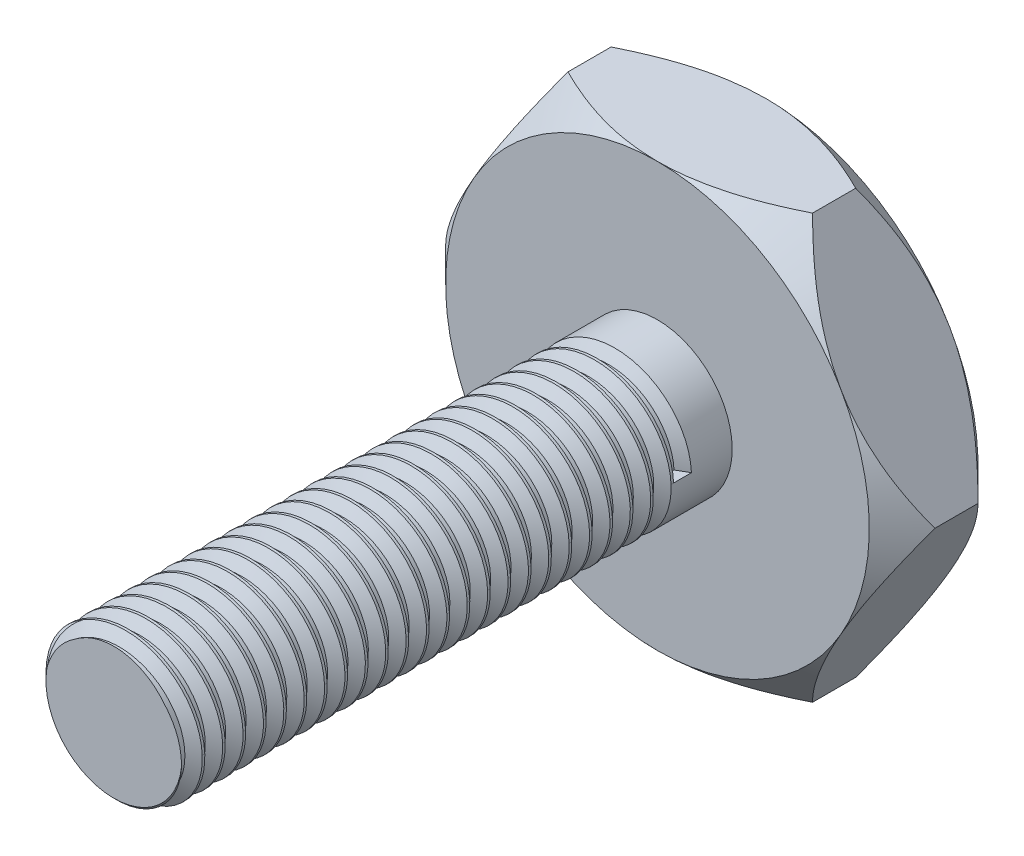
SolidWorks part; units mm, degrees
ref_plane "Plan de face" through (0, 0, 0) normal (0, 0, 1) x (1, 0, 0)
ref_plane "Plan de dessus" through (0, 0, 0) normal (0, 1, 0) x (1, 0, 0)
ref_plane "Plan de droite" through (0, 0, 0) normal (1, 0, 0) x (0, 0, -1)
sketch "Esquisse1" plane through (0, 0, 0) normal (0, 0, 1) x (1, 0, 0)
  line L2 (-9, 15.5885) -> (-18, 0)
  line L3 (-18, 0) -> (-9, -15.5885)
  line L4 (-9, -15.5885) -> (9, -15.5885)
  line L5 (9, -15.5885) -> (18, 0)
  line L6 (18, 0) -> (9, 15.5885)
  line L7 (9, 15.5885) -> (-9, 15.5885)
  circle A0 centre (0, 0) radius 15.5885 construction
  dimension "D1" = 18
extrude "Boss.-Extru.2" add sketch "Esquisse1" along normal mid plane 8
sketch "Esquisse4" plane through (0, 0, 4) normal (0, 0, 1) x (1, 0, 0)
  line L0 (-9, 15.5885) -> (-18, 0) construction
  circle A0 centre (0, 0) radius 15.5885
extrude "Enlèv. mat.-Extru.2" cut sketch "Esquisse4" against normal through all draft 45 flip side to cut
mirror "Symétrie4" about plane through (0, 0, 0) normal (0, 0, 1) of "Enlèv. mat.-Extru.2"
sketch "Esquisse5" plane through (0, 0, 4) normal (0, 0, 1) x (1, 0, 0)
  circle A0 centre (0, 0) radius 5.5
  dimension "D1" = 11
extrude "Boss.-Extru.4" add sketch "Esquisse5" along normal blind 40
chamfer "Chanfrein1" distance 0.5 angle 45 1 edges at (5.5, 0, 44)
thread "Filetage2" pitch 1.5 method cut profile "Profil de filetage2" start angle 0, offset 3, length 0, pitch 1.5, diameter 11
ref_plane "Plan2" through (5.5, 0, 7) normal (0, -1, 0) x (1, 0, 0)
sketch "Profil de filetage2" plane through (5.5, 0, 7) normal (0, -1, 0) x (1, 0, 0)
  line L0 (0, 0) -> (0, 1.5) construction
  line L11 (0, 0) -> (0, 1.3125)
  line L12 (0, 1.3125) -> (-0.8119, 0.8437)
  line L13 (-0.8119, 0.8437) -> (-0.8119, 0.4687)
  line L15 (-0.8119, 0.4687) -> (0, 0)
  line L17 (-0.8119, 0.6562) -> (0, 0.6562) construction
  point P2 (0, 0)
  dimension "Pitch" = 1.5
  dimension "Profile_Angle" = 60
  dimension "Profile_Land" = 0.375
  dimension "Profile_Height" = 0.8119
